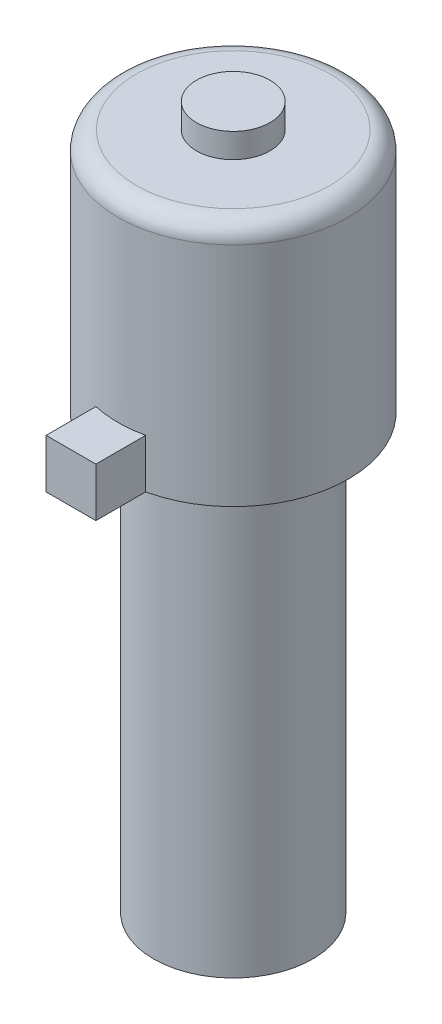
SolidWorks part; units mm, degrees
ref_plane "Front Plane" through (0, 0, 0) normal (0, 0, 1) x (1, 0, 0)
ref_plane "Top Plane" through (0, 0, 0) normal (0, 1, 0) x (1, 0, 0)
ref_plane "Right Plane" through (0, 0, 0) normal (1, 0, 0) x (0, 0, -1)
sketch "Sketch1" plane through (0, 0, 0) normal (0, 1, 0) x (1, 0, 0)
  circle A0 centre (0, 0) radius 3.25
  dimension "D1" = 6.5
extrude "Boss-Extrude1" add sketch "Sketch1" along normal blind 17.686 contours A0
sketch "Sketch2" plane through (0, 0, 0) normal (0, -1, 0) x (1, 0, 0)
  circle A1 centre (0, 0) radius 1.75
  dimension "D1" = 3.5
extrude "Cut-Extrude1" [suppressed] cut sketch "Sketch2" against normal blind 2.5
sketch "Sketch6" plane through (0, 17.686, 0) normal (0, 1, 0) x (1, 0, 0)
  circle A0 centre (0, 0) radius 4.7
  dimension "D1" = 9.4
extrude "Boss-Extrude2" add sketch "Sketch6" along normal blind 10 contours A0
fillet "Fillet2" radius 0.75 1 edges at (0, 27.686, 4.7)
sketch "Sketch7" plane through (0, 27.686, 0) normal (0, 1, 0) x (1, 0, 0)
  circle A0 centre (0, 0) radius 1.5
  dimension "D1" = 3
extrude "Boss-Extrude3" add sketch "Sketch7" along normal blind 1
sketch "Sketch8" plane through (0, 17.686, 0) normal (0, -1, 0) x (1, 0, 0)
  line L0 (0, 4.7) -> (0, -4.7) construction
  line L1 (-1.016, 4.5889) -> (-1.016, 6.6209)
  line L2 (-1.016, 6.6209) -> (1.016, 6.6209)
  line L3 (1.016, 6.6209) -> (1.016, 4.5889)
  circle A0 centre (0, 0) radius 4.7 construction
  circle A2 centre (0, 0) radius 4.7
  arc A3 (1.016, 4.5889) -> (-1.016, 4.5889) centre (0, 0) ccw
  point P9 (0, 0)
  dimension "D2" = 2.032
  dimension "D3" = 2.032
  dimension "D1" = 0
extrude "Boss-Extrude4" add sketch "Sketch8" against normal blind 2
